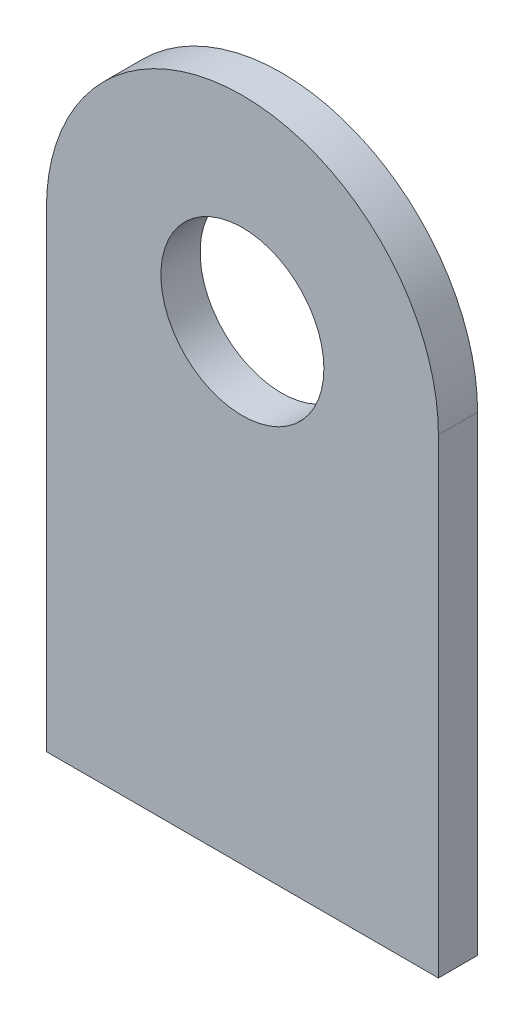
SolidWorks part; units mm, degrees
material "ASTM A36 Steel"
ref_plane "X-Y Datum" through (0, 0, 0) normal (0, 0, 1) x (1, 0, 0)
ref_plane "X-Z Datum" through (0, 0, 0) normal (0, 1, 0) x (1, 0, 0)
ref_plane "Y-Z Datum" through (0, 0, 0) normal (1, 0, 0) x (0, 0, -1)
sketch "Sketch1" plane through (0, 0, 0) normal (0, 0, 1) x (1, 0, 0)
  line L0 (-7.9375, 0) -> (-7.9375, -25.4)
  line L1 (-7.9375, -25.4) -> (7.9375, -25.4)
  line L2 (7.9375, -25.4) -> (7.9375, 0)
  circle A0 centre (0, 0) radius 7.9375
  circle A1 centre (0, 0) radius 3
  dimension "D1" = 6
  dimension "D2" = 15.875
  dimension "D3" = 25.4
extrude "Boss-Extrude1" add sketch "Sketch1" along normal blind 1.5875 contours A0 A1 | A0 L0 L1 L2 | A1 region at (0, -15.7352, 0) region at (0, 7.713, 0) region at (0, 0, 0)
hole_wizard "M6 Clearance Hole1" positions "Sketch2" profile "Sketch3" hole size "M6" standard "ANSI Metric" end condition through all
sketch "Sketch2" plane through (0, 0, 1.5875) normal (0, 0, 1) x (1, 0, 0)
  point P0 (0, 0)
sketch "Sketch3" plane through (0, 0, 1.5875) normal (1, 0, 0) x (0, -1, 0)
  line L0 (0, 0) -> (0, 1.5875)
  line L1 (0, 1.5875) -> (3.3, 1.5875)
  line L2 (3.3, 1.5875) -> (3.3, 0)
  line L5 (3.3, 0) -> (0, 0)
  line L11 (0, -6.35) -> (0, 107.95) construction
  dimension "Thru Hole Dia." = 6.6
  dimension "Thru Hole Depth" = 1.5875
sketch "Sketch4" [suppressed] plane through (0, 0, 2.54) normal (0, 0, 1) x (1, 0, 0)
  line L1 (57.1174, 89.0913) -> (2.6108, -25.4)
  line L3 (1.0953, -29.3967) -> (-107.8628, 152.3221)
  line M3 (-7.9375, 0) -> (-7.9375, -25.4)
  line M4 (-7.9375, -25.4) -> (7.9375, -25.4)
  line M5 (7.9375, -25.4) -> (7.9375, 0)
extrude "Cut-Extrude1" [suppressed] cut sketch "Sketch4" against normal through all contours L3 M4 M3 | L1 M5 M4
sketch "Sketch5" plane through (0, 0, 1.5875) normal (0, 0, 1) x (1, 0, 0)
  line L0 (-7.9375, 0) -> (-7.9375, -25.4) construction
  line L1 (7.9375, -25.4) -> (-7.9375, -25.4)
  line L2 (7.9375, -25.4) -> (7.9375, -19.05)
  line L3 (7.9375, -19.05) -> (-7.9375, -19.05)
  line L4 (-7.9375, -25.4) -> (-7.9375, -19.05)
  dimension "D1" = 6.35
extrude "Cut-Extrude2" cut sketch "Sketch5" against normal through all
sketch "Sketch6" [suppressed] plane through (0, 0, 0) normal (0, 0, -1) x (-1, 0, 0)
  spline S0 degree 3 poles (12.0303, -22.8994) (1.6525, 0.2838) (-38.2843, -17.5937) (-27.9064, -40.7769) (-17.5286, -63.9601) (22.4081, -46.0826) (12.0303, -22.8994) (1.6525, 0.2838) (-38.2843, -17.5937) knots -0.5 0 0 0 0.5 0.5 0.5 1 1 1 1.5 1.5 1.5 weights 1 0.333333 0.333333 1 0.333333 0.333333 1 0.333333 0.333333 only from (12.0303, -22.8994) to (12.0303, -22.8994)
  spline S1 degree 3 poles (12.0303, -22.8994) (1.6525, 0.2838) (-38.2843, -17.5937) (-27.9064, -40.7769) (-17.5286, -63.9601) (22.4081, -46.0826) (12.0303, -22.8994) (1.6525, 0.2838) (-38.2843, -17.5937) knots -0.5 0 0 0 0.5 0.5 0.5 1 1 1 1.5 1.5 1.5 weights 1 0.333333 0.333333 1 0.333333 0.333333 1 0.333333 0.333333 only from (12.0303, -22.8994) to (12.0303, -22.8994)
extrude "Cut-Extrude3" [suppressed] cut sketch "Sketch6" against normal through all
